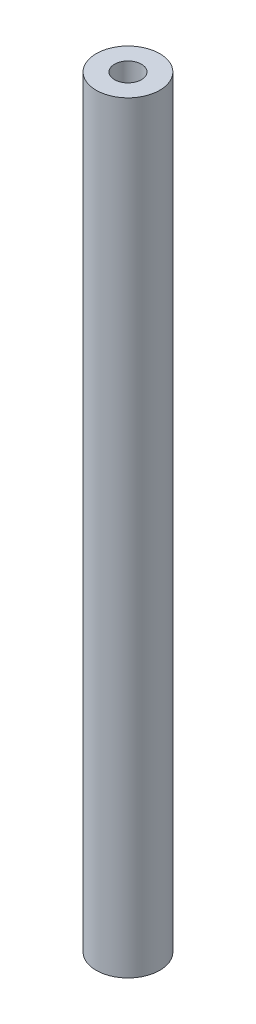
SolidWorks part; units mm, degrees
material "6061-T6 (SS)"
ref_plane "Front Plane" through (0, 0, 0) normal (0, 0, 1) x (1, 0, 0)
ref_plane "Top Plane" through (0, 0, 0) normal (0, 1, 0) x (1, 0, 0)
ref_plane "Right Plane" through (0, 0, 0) normal (1, 0, 0) x (0, 0, -1)
sketch "Sketch1" plane through (0, 0, 0) normal (0, 1, 0) x (1, 0, 0)
  circle A1 centre (0, 0) radius 4.7625
  dimension "D2" = 9.525
extrude "Boss-Extrude1" add sketch "Sketch1" along normal mid plane 114.3
hole_wizard "#10-32 Tapped Hole1" positions "3DSketch1" profile "Sketch2" tap size "#10-32" standard "ANSI Inch"
sketch3d "3DSketch1"
  line L0 (0, 57.15, 0) -> (0, -57.15, 0) construction
  point P0 (0, 57.15, 0)
  point P4 (0, -57.15, 0)
sketch "Sketch2" plane through (0, 57.15, 0) normal (1, 0, 0) x (0, 0, 1)
  line L0 (0, 0) -> (0, 13.1513)
  line L1 (0, 13.1513) -> (2.0193, 11.938)
  line L2 (2.0193, 11.938) -> (2.0193, 0)
  line L5 (2.0193, 0) -> (0, 0)
  line L10 (0, 13.1513) -> (-2.0193, 11.938) construction
  line L11 (0, -6.35) -> (0, 107.95) construction
  dimension "Tap Drill Dia." = 4.0386
  dimension "Tap Drill Depth" = 11.938
  dimension "Drill Angle" = 118
cosmetic thread "Hole Thread1"
cosmetic thread "Hole Thread2"
